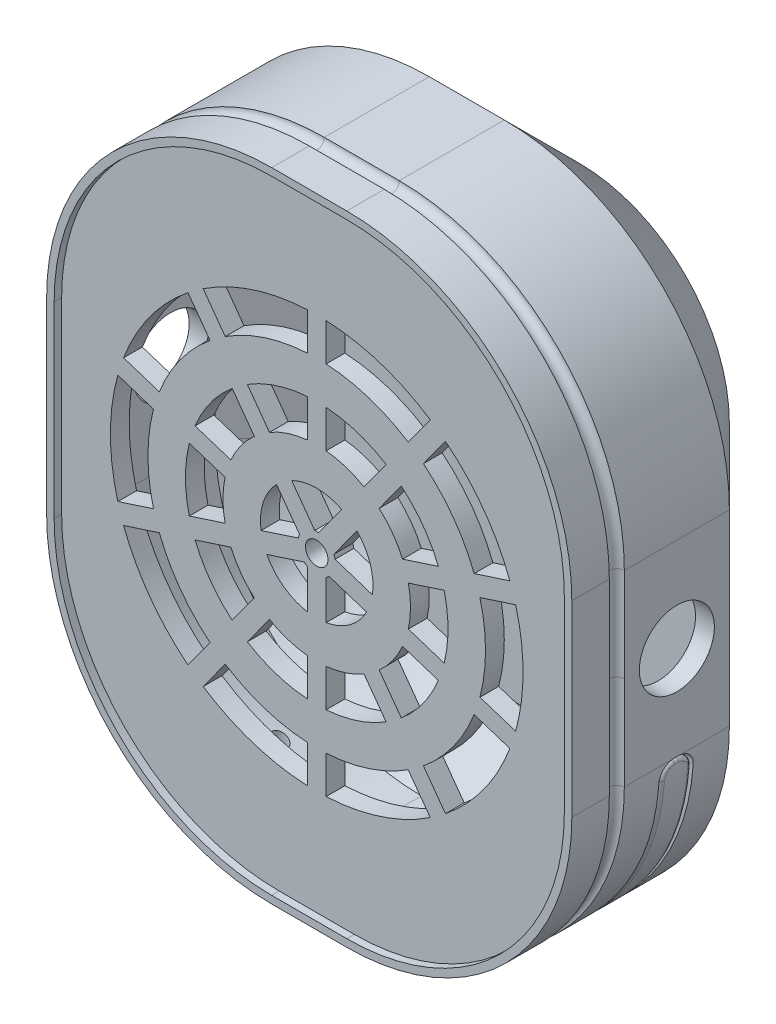
SolidWorks part; units mm, degrees
ref_plane "Front Plane" through (0, 0, 0) normal (0, 0, 1) x (1, 0, 0)
ref_plane "Top Plane" through (0, 0, 0) normal (0, 1, 0) x (1, 0, 0)
ref_plane "Right Plane" through (0, 0, 0) normal (1, 0, 0) x (0, 0, -1)
sketch "Sketch2" plane through (0, 0, 0) normal (0, 0, 1) x (1, 0, 0)
  line L1 (5, -42.5) -> (-5, -42.5)
  line L2 (35, -12.5) -> (35, 12.5)
  line L3 (5, 42.5) -> (-5, 42.5)
  line L4 (-35, -12.5) -> (-35, 12.5)
  line L5 (35, -42.5) -> (-35, 42.5) construction
  line L6 (35, 42.5) -> (-35, -42.5) construction
  arc A0 (-5, -42.5) -> (-35, -12.5) centre (-5, -12.5) cw
  arc A1 (5, -42.5) -> (35, -12.5) centre (5, -12.5) ccw
  arc A2 (35, 12.5) -> (5, 42.5) centre (5, 12.5) ccw
  arc A3 (-5, 42.5) -> (-35, 12.5) centre (-5, 12.5) ccw
  point P0 (0, 0)
  dimension "D1" = 30
extrude "Boss-Extrude1" add sketch "Sketch2" along normal blind 20
sketch "Sketch3" plane through (0, 0, 0) normal (0, 0, -1) x (-1, 0, 0)
  line L8 (25, -12.5) -> (25, 12.5)
  line L9 (5, 32.5) -> (-5, 32.5)
  line L10 (-25, 12.5) -> (-25, -12.5)
  line L11 (-5, -32.5) -> (5, -32.5)
  line L12 (25, -12.5) -> (25, 12.5)
  line L13 (5, 32.5) -> (-5, 32.5)
  line L14 (-25, 12.5) -> (-25, -12.5)
  line L15 (-5, -32.5) -> (5, -32.5)
  arc A8 (5, -32.5) -> (25, -12.5) centre (5, -12.5) ccw
  arc A9 (25, 12.5) -> (5, 32.5) centre (5, 12.5) ccw
  arc A10 (-5, 32.5) -> (-25, 12.5) centre (-5, 12.5) ccw
  arc A11 (-25, -12.5) -> (-5, -32.5) centre (-5, -12.5) ccw
  arc A12 (5, -32.5) -> (25, -12.5) centre (5, -12.5) ccw
  arc A13 (25, 12.5) -> (5, 32.5) centre (5, 12.5) ccw
  arc A14 (-5, 32.5) -> (-25, 12.5) centre (-5, 12.5) ccw
  arc A15 (-25, -12.5) -> (-5, -32.5) centre (-5, -12.5) ccw
  dimension "D1" = 10
extrude "Boss-Extrude2" add sketch "Sketch3" along normal blind 10
chamfer "Chamfer1" distance 10 angle 45 8 edges at (0, -32.5, 0) (-19.1421, -26.6421, 0) (19.1421, -26.6421, 0) (-25, 0, 0) (25, 0, 0) (-19.1421, 26.6421, 0) (19.1421, 26.6421, 0) (0, 32.5, 0)
ref_plane "Plane1" through (0, 0, 15) normal (0, 0, 1) x (1, 0, 0)
sketch "Sketch5" plane through (0, 0, 15) normal (0, 0, 1) x (1, 0, 0)
  line L4 (-5, -42.5) -> (5, -42.5)
  line L5 (35, -12.5) -> (35, 12.5)
  line L6 (5, 42.5) -> (-5, 42.5)
  line L7 (-35, 12.5) -> (-35, -12.5)
  line L8 (-5, -42.5) -> (5, -42.5)
  line L9 (35, -12.5) -> (35, 12.5)
  line L10 (5, 42.5) -> (-5, 42.5)
  line L11 (-35, 12.5) -> (-35, -12.5)
  arc A4 (-35, -12.5) -> (-5, -42.5) centre (-5, -12.5) ccw
  arc A5 (5, -42.5) -> (35, -12.5) centre (5, -12.5) ccw
  arc A6 (35, 12.5) -> (5, 42.5) centre (5, 12.5) ccw
  arc A7 (-5, 42.5) -> (-35, 12.5) centre (-5, 12.5) ccw
  arc A8 (-35, -12.5) -> (-5, -42.5) centre (-5, -12.5) ccw
  arc A9 (5, -42.5) -> (35, -12.5) centre (5, -12.5) ccw
  arc A10 (35, 12.5) -> (5, 42.5) centre (5, 12.5) ccw
  arc A11 (-5, 42.5) -> (-35, 12.5) centre (-5, 12.5) ccw
  dimension "D1" = 0
sketch "Sketch6" plane through (0, 0, 0) normal (0, 1, 0) x (1, 0, 0)
  line L0 (5, -15) -> (35, -15) construction
  line L1 (5, -15) -> (35, -15) construction
  circle A0 centre (35, -15) radius 1
  dimension "D1" = 2
sweep "Cut-Sweep1" cut profiles "Sketch6" path "Sketch5"
shell "Shell1" thickness 2.5
sketch "Sketch8" plane through (0, 0, 20) normal (0, 0, 1) x (1, 0, 0)
  line L4 (-35, 12.5) -> (-10.6269, 12.5) construction
  line L5 (0, 17.5) -> (0, 27.5) construction
  line L7 (15.1361, 22.9597) -> (0.2613, 2.4863)
  line L9 (-1.25, 27.4716) -> (-1.25, 7.3951)
  line L11 (1.25, 27.4716) -> (1.25, 7.3951)
  line L12 (17.1587, 21.4902) -> (2.2839, 1.0168)
  line L13 (25.7408, 9.678) -> (6.6469, 3.474)
  line L14 (26.5133, 7.3004) -> (7.4194, 1.0964)
  line L15 (26.5133, -7.3004) -> (2.4454, 0.5198)
  line L16 (25.7408, -9.678) -> (1.6728, -1.8579)
  line L17 (17.1587, -21.4902) -> (5.358, -5.248)
  line L18 (15.1361, -22.9597) -> (3.3355, -6.7175)
  line L19 (1.25, -27.4716) -> (1.25, -2.1651)
  line L20 (-1.25, -27.4716) -> (-1.25, -2.1651)
  line L21 (-15.1361, -22.9597) -> (-3.3355, -6.7175)
  line L22 (-17.1587, -21.4902) -> (-5.358, -5.248)
  line L23 (-25.7408, -9.678) -> (-1.6728, -1.8579)
  line L24 (-26.5133, -7.3004) -> (-2.4454, 0.5198)
  line L25 (-26.5133, 7.3004) -> (-7.4194, 1.0964)
  line L26 (-25.7408, 9.678) -> (-6.6469, 3.474)
  line L27 (-17.1587, 21.4902) -> (-2.2839, 1.0168)
  line L28 (-15.1361, 22.9597) -> (-0.2613, 2.4863)
  line L29 (-7.5367, 12.5) -> (0, 12.5) construction
  line L30 (1.25, 12.5) -> (7.5367, 12.5) construction
  line L31 (10.6269, 12.5) -> (35, 12.5) construction
  circle A0 centre (0, 0) radius 2.5
  arc A1 (1.25, -7.3951) -> (3.3355, -6.7175) centre (0, 0) ccw
  arc A2 (1.25, -12.4373) -> (6.2992, -10.7968) centre (0, 0) ccw
  arc A3 (1.25, -17.4553) -> (9.2487, -14.8564) centre (0, 0) ccw
  circle A4 centre (0, 0) radius 7.5
  arc A8 (1.25, -22.4653) -> (20.9795, -8.131) centre (0, 0) ccw
  circle A9 centre (0, 0) radius 27.5
  circle A10 centre (0, 0) radius 27.5
  circle A11 centre (0, 0) radius 27.5
  circle A12 centre (0, 0) radius 27.5
  circle A13 centre (0, 0) radius 27.5
  circle A14 centre (0, 0) radius 27.5
  circle A15 centre (0, 0) radius 27.5
  circle A16 centre (0, 0) radius 27.5
  circle A17 centre (0, 0) radius 27.5
  circle A18 centre (0, 0) radius 27.5
  circle A19 centre (0, 0) radius 7.5 construction
  circle A20 centre (0, 0) radius 12.5 construction
  circle A21 centre (0, 0) radius 17.5 construction
  circle A22 centre (0, 0) radius 22.5 construction
  arc A23 (-6.6469, -3.474) -> (-5.358, -5.248) centre (0, 0) ccw
  arc A24 (-11.4423, -5.0322) -> (-8.3218, -9.3273) centre (0, 0) ccw
  arc A25 (-16.2147, -6.5828) -> (-11.2712, -13.3869) centre (0, 0) ccw
  arc A26 (-20.9795, -8.131) -> (-14.216, -17.44) centre (0, 0) ccw
  arc A27 (-3.3355, -6.7175) -> (-1.25, -7.3951) centre (0, 0) ccw
  arc A28 (-6.2992, -10.7968) -> (-1.25, -12.4373) centre (0, 0) ccw
  arc A29 (-9.2487, -14.8564) -> (-1.25, -17.4553) centre (0, 0) ccw
  arc A30 (-12.1935, -18.9095) -> (-1.25, -22.4653) centre (0, 0) ccw
  arc A31 (-7.4194, 1.0964) -> (-7.4194, -1.0964) centre (0, 0) ccw
  arc A32 (-12.2149, 2.6545) -> (-12.2149, -2.6545) centre (0, 0) ccw
  arc A33 (-16.9872, 4.2052) -> (-16.9872, -4.2052) centre (0, 0) ccw
  arc A34 (-21.752, 5.7533) -> (-21.752, -5.7533) centre (0, 0) ccw
  arc A35 (-5.358, 5.248) -> (-6.6469, 3.474) centre (0, 0) ccw
  arc A36 (-8.3218, 9.3273) -> (-11.4423, 5.0322) centre (0, 0) ccw
  arc A37 (-11.2712, 13.3869) -> (-16.2147, 6.5828) centre (0, 0) ccw
  arc A38 (-14.216, 17.44) -> (-20.9795, 8.131) centre (0, 0) ccw
  arc A39 (-1.25, 7.3951) -> (-3.3355, 6.7175) centre (0, 0) ccw
  arc A40 (0, 12.5) -> (-6.2992, 10.7968) centre (0, 0) ccw
  arc A41 (-1.25, 17.4553) -> (-9.2487, 14.8564) centre (0, 0) ccw
  arc A42 (-1.25, 22.4653) -> (-12.1935, 18.9095) centre (0, 0) ccw
  arc A43 (3.3355, 6.7175) -> (1.25, 7.3951) centre (0, 0) ccw
  arc A44 (6.2992, 10.7968) -> (1.25, 12.4373) centre (0, 0) ccw
  arc A45 (9.2487, 14.8564) -> (0, 17.5) centre (0, 0) ccw
  arc A46 (12.1935, 18.9095) -> (0, 22.5) centre (0, 0) ccw
  arc A47 (6.6469, 3.474) -> (5.358, 5.248) centre (0, 0) ccw
  arc A48 (11.4423, 5.0322) -> (8.3218, 9.3273) centre (0, 0) ccw
  arc A49 (16.2147, 6.5828) -> (11.2712, 13.3869) centre (0, 0) ccw
  arc A50 (20.9795, 8.131) -> (14.216, 17.44) centre (0, 0) ccw
  arc A51 (7.4194, -1.0964) -> (7.4194, 1.0964) centre (0, 0) ccw
  arc A52 (12.2149, -2.6545) -> (12.2149, 2.6545) centre (0, 0) ccw
  arc A53 (16.9872, -4.2052) -> (16.9872, 4.2052) centre (0, 0) ccw
  arc A54 (21.752, -5.7533) -> (21.752, 5.7533) centre (0, 0) ccw
  arc A55 (5.358, -5.248) -> (6.6469, -3.474) centre (0, 0) ccw
  arc A56 (8.3218, -9.3273) -> (11.4423, -5.0322) centre (0, 0) ccw
  arc A57 (11.2712, -13.3869) -> (16.2147, -6.5828) centre (0, 0) ccw
  circle A58 centre (0, 0) radius 1.5
  point P71 (0, 0)
  dimension "D1" = 5
  dimension "D7" = 1
  dimension "D6" = 1.25
  dimension "D2" = 5
  dimension "D3" = 5
  dimension "D4" = 5
  dimension "D5" = 5
  dimension "D8" = 10
extrude "Cut-Extrude3" cut sketch "Sketch8" against normal blind 5 contours A34 L25 A9 L24 | L25 A33 L24 A32 | A38 L27 A9 L26 | L27 A37 L26 A36 | A42 L9 A9 L28 | L9 A41 L28 A40 | A46 L7 A9 L11 | L7 A45 L11 A44 | A50 L13 A9 L12 | L13 A49 L12 A48 | L15 A53 L14 A52 | A54 L15 A9 L14 | L17 A9 L16 A8 | L17 A57 L16 A56 | L19 A3 L18 A2 | L21 A29 L20 A28 | A30 L21 A9 L20 | L19 A9 L18 A8 | A26 L23 A9 L22 | L23 A25 L22 A24 | A58 region at (7.666, 23.5936, 20) region at (20.0699, 14.5817, 20) region at (4.6518, 14.3167, 20) region at (-7.666, 23.5936, 20) region at (12.1785, 8.8482, 20) region at (24.8078, 0, 20) region at (-4.6518, 14.3167, 20) region at (-20.0699, 14.5817, 20) region at (15.0535, 0, 20) region at (20.0699, -14.5817, 20) region at (-12.1785, 8.8482, 20) region at (-24.8078, 0, 20) region at (12.1785, -8.8482, 20) region at (7.666, -23.5936, 20) region at (-15.0535, 0, 20) region at (-20.0699, -14.5817, 20) region at (4.6518, -14.3167, 20) region at (-7.666, -23.5936, 20) region at (-12.1785, -8.8482, 20) region at (-4.6518, -14.3167, 20) region at (0, 0, 20)
extrude "Cut-Extrude4" cut sketch "Sketch8<5>" against normal blind 5 contours A4 L24 A0 L27 | A4 L28 A0 L7 | A4 L12 A0 L15 | A1 A4 L16 A0 L19 | A4 L20 A0 L23 region at (0, 5.5485, 20) region at (5.2769, 1.7146, 20) region at (-5.2769, 1.7146, 20) region at (3.2613, -4.4888, 20) region at (-3.2613, -4.4888, 20)
sketch "Sketch8<5>" plane through (0, 0, 20) normal (0, 0, 1) x (1, 0, 0) same geometry as "Sketch8"
sketch "Sketch9" plane through (-35, 0, 0) normal (-1, 0, 0) x (0, 0, 1)
  line L0 (0, 12.5) -> (14, -12.5) construction
  circle A0 centre (7, 0) radius 5
extrude "Cut-Extrude5" cut sketch "Sketch9" against normal through all both and the other way through all
sketch "Sketch10" plane through (-35, 0, 0) normal (-1, 0, 0) x (0, 0, 1)
  line L0 (7, 12.5) -> (7, 15.6961) construction
  line L1 (14, 12.5) -> (0, 12.5) construction
  line L2 (6, 12.5) -> (6, 15.6961)
  line L3 (8, 12.5) -> (8, 15.6961)
  arc A0 (6, 12.5) -> (8, 12.5) centre (7, 12.5) ccw
  arc A1 (8, 15.6961) -> (6, 15.6961) centre (7, 15.6961) ccw
  point P4 (7, 14.098)
extrude "Cut-Extrude6" cut sketch "Sketch10" against normal blind 5 and the other way through all
sketch "Sketch16" plane through (0, 0, 20) normal (0, 0, 1) x (1, 0, 0)
  line L8 (-5, -41.5) -> (5, -41.5)
  line L9 (34, -12.5) -> (34, 12.5)
  line L10 (5, 41.5) -> (-5, 41.5)
  line L11 (-34, 12.5) -> (-34, -12.5)
  line L12 (-5, -41.5) -> (5, -41.5)
  line L13 (34, -12.5) -> (34, 12.5)
  line L14 (5, 41.5) -> (-5, 41.5)
  line L15 (-34, 12.5) -> (-34, -12.5)
  line L16 (-5, -42.5) -> (5, -42.5)
  line L17 (35, -12.5) -> (35, 12.5)
  line L18 (5, 42.5) -> (-5, 42.5)
  line L19 (-35, 12.5) -> (-35, -12.5)
  line L20 (-5, -42.5) -> (5, -42.5)
  line L21 (35, -12.5) -> (35, 12.5)
  line L22 (5, 42.5) -> (-5, 42.5)
  line L23 (-35, 12.5) -> (-35, -12.5)
  arc A8 (-34, -12.5) -> (-5, -41.5) centre (-5, -12.5) ccw
  arc A9 (5, -41.5) -> (34, -12.5) centre (5, -12.5) ccw
  arc A10 (34, 12.5) -> (5, 41.5) centre (5, 12.5) ccw
  arc A11 (-5, 41.5) -> (-34, 12.5) centre (-5, 12.5) ccw
  arc A12 (-34, -12.5) -> (-5, -41.5) centre (-5, -12.5) ccw
  arc A13 (5, -41.5) -> (34, -12.5) centre (5, -12.5) ccw
  arc A14 (34, 12.5) -> (5, 41.5) centre (5, 12.5) ccw
  arc A15 (-5, 41.5) -> (-34, 12.5) centre (-5, 12.5) ccw
  arc A16 (-35, -12.5) -> (-5, -42.5) centre (-5, -12.5) ccw
  arc A17 (5, -42.5) -> (35, -12.5) centre (5, -12.5) ccw
  arc A18 (35, 12.5) -> (5, 42.5) centre (5, 12.5) ccw
  arc A19 (-5, 42.5) -> (-35, 12.5) centre (-5, 12.5) ccw
  arc A20 (-35, -12.5) -> (-5, -42.5) centre (-5, -12.5) ccw
  arc A21 (5, -42.5) -> (35, -12.5) centre (5, -12.5) ccw
  arc A22 (35, 12.5) -> (5, 42.5) centre (5, 12.5) ccw
  arc A23 (-5, 42.5) -> (-35, 12.5) centre (-5, 12.5) ccw
  dimension "D1" = 1
  dimension "D2" = 0
extrude "Boss-Extrude8" add sketch "Sketch16" along normal blind 1
sketch "Sketch17" plane through (0, -42.5, 0) normal (0, -1, 0) x (1, 0, 0)
  circle A2 centre (-12.7584, 7.2431) radius 0.5
  circle A3 centre (-17.7381, 7.2431) radius 1
extrude "Cut-Extrude7" cut sketch "Sketch17" against normal blind 10
sketch "Sketch18" plane through (0, -42.5, 0) normal (0, -1, 0) x (1, 0, 0)
  line L0 (22.4882, 9.0791) -> (39.0489, 9.0791)
  line L1 (22.4882, 9.3291) -> (39.0489, 9.3291)
  line L2 (20.4882, 7.3291) -> (20.4882, 6.7492)
  line L3 (22.4882, 4.7492) -> (39.0489, 4.7492)
  line L4 (39.0489, 9.3291) -> (39.0489, 4.7492)
  line L5 (20.7382, 7.3291) -> (20.7382, 6.7492)
  line L6 (22.4882, 4.9992) -> (39.0489, 4.9992)
  arc A0 (20.4882, 6.7492) -> (22.4882, 4.7492) centre (22.4882, 6.7492) ccw
  arc A1 (22.4882, 9.3291) -> (20.4882, 7.3291) centre (22.4882, 7.3291) ccw
  arc A2 (22.4882, 9.0791) -> (20.7382, 7.3291) centre (22.4882, 7.3291) ccw
  arc A3 (20.7382, 6.7492) -> (22.4882, 4.9992) centre (22.4882, 6.7492) ccw
  dimension "D1" = 2
  dimension "D2" = 0.25
extrude "Cut-Extrude8" cut sketch "Sketch18" against normal blind 15 contours A3 L5 A2 L0 L4 L1 A1 L2 A0 L3 L6 region at (21.1156, -42.5, 8.7017)
sketch "Sketch19" plane through (0, 0, 0) normal (1, 0, 0) x (0, 0, -1)
  line L0 (-9.0791, -27.25) -> (-9.0791, -27.5)
  line L1 (-9.3291, -27.5) -> (-9.0791, -27.5)
  line L2 (-9.3291, -27.5) -> (-9.3291, -14.5)
  line L3 (-7.3291, -12.5) -> (-6.7492, -12.5)
  line L4 (-4.7492, -27.5) -> (-4.7492, -14.5)
  line L5 (-4.9992, -27.25) -> (-4.9992, -27.5)
  line L6 (-4.9992, -27.5) -> (-4.7492, -27.5)
  line L7 (-9.3291, -27.5) -> (-4.7492, -27.5) construction
  line L8 (-9.0791, -27.25) -> (-9.0791, -14.5)
  line L9 (-7.3291, -12.75) -> (-6.7492, -12.75)
  line L10 (-4.9992, -27.25) -> (-4.9992, -14.5)
  line L13 (-9.0791, -27.25) -> (-4.9992, -27.25) construction
  arc A0 (-6.7492, -12.5) -> (-4.7492, -14.5) centre (-6.7492, -14.5) cw
  arc A1 (-9.3291, -14.5) -> (-7.3291, -12.5) centre (-7.3291, -14.5) cw
  arc A2 (-9.0791, -14.5) -> (-7.3291, -12.75) centre (-7.3291, -14.5) cw
  arc A3 (-6.7492, -12.75) -> (-4.9992, -14.5) centre (-6.7492, -14.5) cw
  dimension "D1" = 2
  dimension "D2" = 0.25
extrude "Cut-Extrude9" cut sketch "Sketch19" along normal through all contours A1 L2 L1 L4 A0 L3 L9 A3 L10 L5 L8 A2 region at (0, -27.375, 9.2359)
sketch "Sketch20" plane through (-35, 0, 0) normal (-1, 0, 0) x (0, 0, 1)
  line L0 (7, 0) -> (7, -22.9104) construction
  circle A0 centre (7, -16.9317) radius 2.2933
  circle A1 centre (7, -16.9317) radius 2.5433
  dimension "D1" = 0.25
extrude "Cut-Extrude11" cut sketch "Sketch20" against normal blind 10
fillet "Fillet1" radius 0.5 1 edges at (-34.7452, -16.4015, 4.7689)
fillet "Fillet2" radius 0.5 8 edges at (31.2176, -27.082, 9.0791) (21.0308, -37.8577, 8.2978) (20.7382, -38.0403, 7.0392) (21.2652, -37.708, 5.4975) (31.2176, -27.082, 4.9992) (34.9933, -13.1334, 5.6561) (34.999, -12.75, 7.0392) (34.9863, -13.4073, 8.6961)
